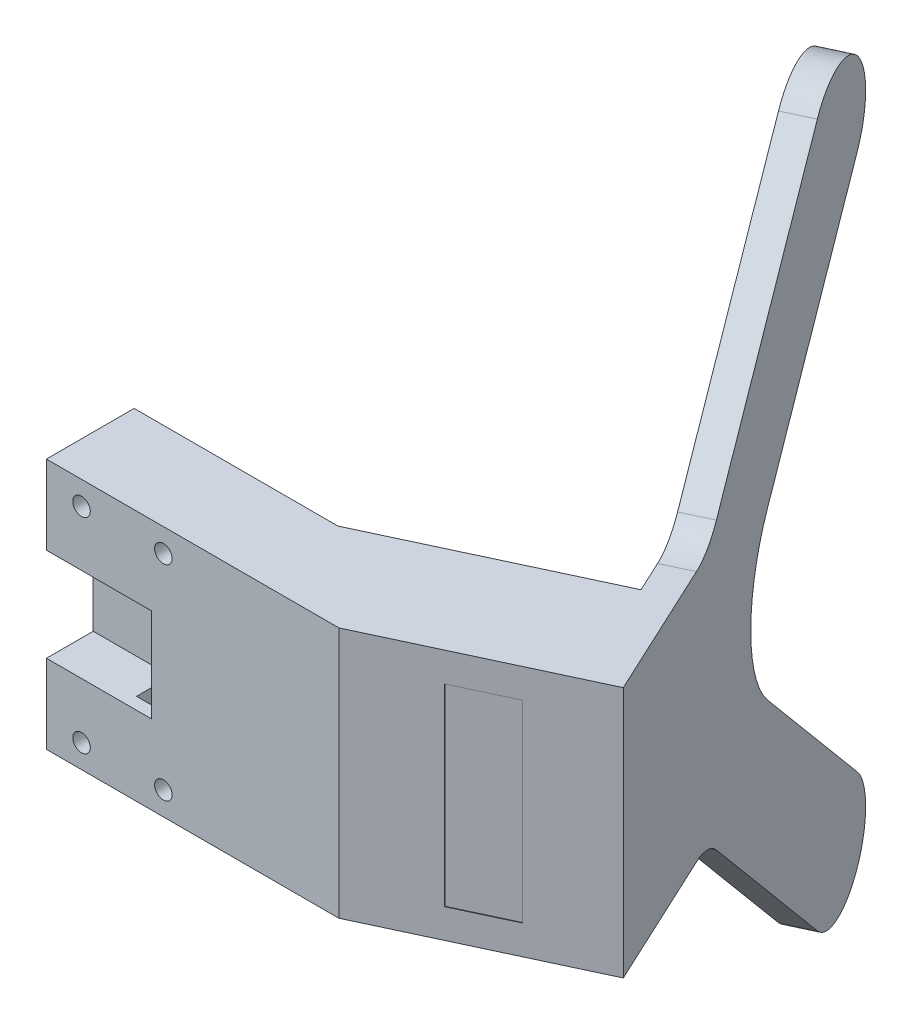
SolidWorks part; units mm, degrees
ref_plane "Ebene vorne" through (0, 0, 0) normal (0, 0, 1) x (1, 0, 0)
ref_plane "Ebene oben" through (0, 0, 0) normal (0, 1, 0) x (1, 0, 0)
ref_plane "Ebene rechts" through (0, 0, 0) normal (1, 0, 0) x (0, 0, -1)
sketch "Skizze1" plane through (0, 0, 0) normal (0, 1, 0) x (1, 0, 0)
  line L0 (0, 0) -> (50, 0)
  line L1 (50, 0) -> (78.6419, 13.356)
  line L2 (78.6419, 13.356) -> (70.1896, 31.4821)
  line L3 (70.1896, 31.4821) -> (34.8436, 15)
  line L4 (34.8436, 15) -> (0, 15)
  line L5 (0, 15) -> (0, 0)
  dimension "D1" = 50
  dimension "D2" = 20
  dimension "D3" = 15
  dimension "D4" = 155
  dimension "D5" = 39
extrude "Aufsatz-Linear austragen1" add sketch "Skizze1" along normal blind 43
sketch "Skizze2" plane through (69.7116, 0, -32.5071) normal (0.9063, 0, -0.4226) x (-0.4226, 0, -0.9063)
  line L0 (-21.1309, 43) -> (8.8691, 43)
  line L1 (-21.1309, 43) -> (-21.1309, 0) construction
  line L2 (-21.1309, 43) -> (-1.1309, 43) construction
  line L3 (8.8691, 43) -> (54.5442, 88.6751)
  line L4 (54.5442, 88.6751) -> (68.6864, 74.533)
  line L5 (68.6864, 74.533) -> (15.6534, 21.5)
  line L6 (15.6534, 21.5) -> (68.6864, -31.533)
  line L7 (68.6864, -31.533) -> (54.5442, -45.6751)
  line L8 (54.5442, -45.6751) -> (8.8691, 0)
  line L9 (8.8691, 0) -> (-21.1309, 0)
  line L10 (-21.1309, 0) -> (-21.1309, 43)
  dimension "D1" = 30
  dimension "D2" = 20
  dimension "D3" = 135
  dimension "D4" = 135
  dimension "D5" = 20
  dimension "D6" = 75
  dimension "D7" = 75
extrude "Aufsatz-Linear austragen2" add sketch "Skizze2" along normal blind 5
sketch "Skizze3" plane through (0, 0, 0) normal (0, 0, 1) x (1, 0, 0)
  line L0 (0, 43) -> (0, 0) construction
  line L1 (0, 43) -> (50, 43) construction
  line L2 (0, 0) -> (50, 0) construction
  circle A0 centre (6, 39) radius 1.5
  circle A1 centre (20, 39) radius 1.5
  circle A2 centre (6, 4) radius 1.5
  circle A3 centre (20, 4) radius 1.5
  dimension "D1" = 3
  dimension "D2" = 6
  dimension "D3" = 4
  dimension "D4" = 14
  dimension "D5" = 4
extrude "Schnitt-Linear austragen1" cut sketch "Skizze3" against normal up to next
sketch "Skizze4" plane through (0, 0, 0) normal (-1, 0, 0) x (0, 0, 1)
  line L0 (0, 43) -> (0, 0) construction
  line L1 (0, 29.5) -> (-8, 29.5)
  line L2 (0, 29.5) -> (0, 13.5)
  line L3 (0, 13.5) -> (-8, 13.5)
  line L4 (-8, 29.5) -> (-8, 13.5)
  line L5 (-15, 43) -> (0, 43) construction
  dimension "D1" = 16
  dimension "D2" = 8
  dimension "D3" = 13.5
extrude "Schnitt-Linear austragen2" cut sketch "Skizze4" against normal blind 18
sketch "Skizze5" plane through (0.4779, 0, 1.025) normal (-0.4226, 0, -0.9063) x (-0.9063, 0, 0.4226)
  line L0 (-76.9183, 43) -> (-76.9183, 0) construction
  line L1 (-75.9183, 41) -> (-45.9183, 41)
  line L2 (-75.9183, 41) -> (-75.9183, 2)
  line L3 (-75.9183, 2) -> (-45.9183, 2)
  line L4 (-45.9183, 41) -> (-45.9183, 2)
  line L5 (-76.9183, 0) -> (-37.9183, 0) construction
  line L6 (-76.9183, 43) -> (-37.9183, 43) construction
  dimension "D1" = 1
  dimension "D2" = 2
  dimension "D3" = 2
  dimension "D4" = 30
extrude "Schnitt-Linear austragen3" cut sketch "Skizze5" against normal blind 18
sketch "Skizze6" plane through (8.0851, 0, 17.3385) normal (-0.4226, 0, -0.9063) x (-0.9063, 0, 0.4226)
  line L0 (-45.9183, 41) -> (-75.9183, 41) construction
  line L1 (-75.9183, 41) -> (-68.9183, 41)
  line L2 (-75.9183, 41) -> (-75.9183, 33.5)
  line L3 (-75.9183, 33.5) -> (-68.9183, 33.5)
  line L4 (-68.9183, 41) -> (-68.9183, 33.5)
  line L5 (-75.9183, 41) -> (-75.9183, 2) construction
  line L7 (-75.9183, 25.5) -> (-68.9183, 25.5)
  line L8 (-75.9183, 25.5) -> (-75.9183, 11.5)
  line L9 (-75.9183, 11.5) -> (-68.9183, 11.5)
  line L10 (-68.9183, 25.5) -> (-68.9183, 11.5)
  line L11 (-75.9183, 2) -> (-68.9183, 2)
  line L12 (-75.9183, 2) -> (-75.9183, 7.5)
  line L13 (-75.9183, 7.5) -> (-68.9183, 7.5)
  line L14 (-68.9183, 2) -> (-68.9183, 7.5)
  dimension "D1" = 7
  dimension "D2" = 7.5
  dimension "D3" = 14
  dimension "D4" = 5.5
  dimension "D5" = 4
extrude "Aufsatz-Linear austragen3" add sketch "Skizze6" along normal blind 4
fillet "Verrundung1" radius 2 4 edges at (69.701, 7.5, -13.6002) (69.701, 11.5, -13.6002) (69.701, 25.5, -13.6002) (69.701, 33.5, -13.6002)
hole_wizard "Ø3.4 (3.4) Durchmesser Bohrung1" positions "Skizze7" profile "Skizze9" hole size "Ø3.4" standard "ANSI Metric"
sketch "Skizze7" plane through (6.3946, 0, 13.7133) normal (-0.4226, 0, -0.9063) x (-0.9063, 0, 0.4226)
  line L0 (-68.9183, 41) -> (-75.9183, 41) construction
  line L1 (-68.9183, 35.5) -> (-68.9183, 41) construction
  line L2 (-75.9183, 2) -> (-68.9183, 2) construction
  line L3 (-68.9183, 2) -> (-68.9183, 5.5) construction
  point P0 (-72.4183, 37)
  point P2 (-72.4183, 22)
  point P4 (-71.4183, 14.1)
  point P6 (-71.4183, 5)
  dimension "D1" = 4
  dimension "D2" = 3.5
  dimension "D3" = 15
  dimension "D4" = 9.1
  dimension "D5" = 3
  dimension "D6" = 2.5
sketch "Skizze9" plane through (72.0278, 37, -16.892) normal (0, 1, 0) x (-0.9063, 0, 0.4226)
  line L0 (0, 0) -> (0, 4)
  line L1 (0, 4) -> (1.7, 4)
  line L2 (1.7, 4) -> (1.7, 0)
  line L5 (1.7, 0) -> (0, 0)
  line L10 (0, 4) -> (-1.7, 4) construction
  line L11 (0, -6.35) -> (0, 107.95) construction
  dimension "Bohrerdurchmesser" = 3.4
  dimension "Bohrungstiefe" = 4
  dimension "Spitzenwinkel" = 180
sketch "Skizze10" plane through (8.0851, 0, 17.3385) normal (-0.4226, 0, -0.9063) x (-0.9063, 0, 0.4226)
  line L0 (-68.9183, 35.5) -> (-68.9183, 41) construction
  line L1 (-68.9183, 38) -> (-58.9183, 38)
  line L2 (-68.9183, 38) -> (-68.9183, 5)
  line L3 (-68.9183, 5) -> (-58.9183, 5)
  line L4 (-58.9183, 38) -> (-58.9183, 5)
  line L5 (-45.9183, 41) -> (-68.9183, 41) construction
  line L6 (-68.9183, 2) -> (-45.9183, 2) construction
  dimension "D1" = 3
  dimension "D2" = 3
  dimension "D3" = 10
extrude "Schnitt-Linear austragen4" cut sketch "Skizze10" against normal blind 1
sketch "Skizze11" plane through (8.9303, 0, 19.1511) normal (0.4226, 0, 0.9063) x (0.9063, 0, -0.4226)
  line L1 (58.9183, 38) -> (68.9183, 38)
  line L2 (58.9183, 38) -> (58.9183, 5)
  line L3 (58.9183, 5) -> (68.9183, 5)
  line L4 (68.9183, 38) -> (68.9183, 5)
extrude "Schnitt-Linear austragen5" cut sketch "Skizze11" against normal blind 0.1
sketch "Skizze12" plane through (0, 2, 0) normal (0, 1, 0) x (1, 0, 0)
  line L0 (49.7012, 2.0674) -> (42.094, 18.3809)
  line L1 (49.7012, 2.0674) -> (42.094, 18.3809) construction
  line L2 (42.094, 18.3809) -> (34.8436, 15)
  line L3 (34.8436, 15) -> (34.8436, 12.5)
  line L5 (29.3436, 2.0674) -> (49.7012, 2.0674)
  line L6 (70.1896, 31.4821) -> (34.8436, 15) construction
  line L7 (34.8436, 12.5) -> (29.3436, 12.5)
  line L8 (29.3436, 12.5) -> (29.3436, 2.0674)
  dimension "D1" = 2.5
  dimension "D2" = 5.5
  dimension "D3" = 65
extrude "Schnitt-Linear austragen7" cut sketch "Skizze12" along normal blind 39
sketch "Skizze15" plane through (29.3436, 0, 0) normal (1, 0, 0) x (0, 0, -1)
  line L0 (2.0674, 41) -> (2.0674, 2) construction
  line L1 (2.0674, 33.5) -> (12.5, 33.5)
  line L2 (2.0674, 33.5) -> (2.0674, 9.5)
  line L3 (2.0674, 9.5) -> (12.5, 9.5)
  line L4 (12.5, 33.5) -> (12.5, 9.5)
  line L5 (12.5, 41) -> (12.5, 2) construction
  line L6 (12.5, 41) -> (2.0674, 41) construction
  dimension "D1" = 24
  dimension "D2" = 7.5
extrude "Schnitt-Linear austragen10" cut sketch "Skizze15" against normal blind 16
sketch "Skizze16" plane through (68.8053, 0, -32.0844) normal (-0.9063, 0, 0.4226) x (0.4226, 0, 0.9063)
  line L0 (15.1309, 41) -> (1.1309, 41) construction
  line L1 (1.1309, 41) -> (3.2309, 41)
  line L2 (1.1309, 41) -> (1.1309, 2)
  line L3 (1.1309, 2) -> (3.2309, 2)
  line L4 (3.2309, 41) -> (3.2309, 2)
  line L5 (1.1309, 41) -> (1.1309, 2) construction
  line L6 (15.1309, 2) -> (1.1309, 2) construction
  dimension "D1" = 2.1
extrude "Schnitt-Linear austragen11" cut sketch "Skizze16" against normal blind 2
fillet "Verrundung2" radius 20 1 edges at (65.362, 21.5, -47.7504)
fillet "Verrundung3" radius 10 6 edges at (68.2292, 43, -41.6017) (68.2292, 0, -41.6017) (42.9493, 74.533, -95.8146) (48.926, 88.6751, -82.9975) (48.926, -45.6751, -82.9975) (42.9493, -31.533, -95.8146)
ref_plane "Ebene2" through (1.3232, 0, 2.8376) normal (-0.4226, 0, -0.9063) x (-0.9063, 0, 0.4226)
sketch "Skizze17" plane through (1.3232, 0, 2.8376) normal (-0.4226, 0, -0.9063) x (-0.9063, 0, 0.4226)
  line L0 (-37.9183, 41) -> (-37.9183, 2) construction
  line L1 (-37.9183, 41) -> (-43.9183, 41)
  line L2 (-37.9183, 41) -> (-37.9183, 35)
  line L3 (-37.9183, 35) -> (-43.9183, 35)
  line L4 (-43.9183, 41) -> (-43.9183, 35)
  line L5 (-68.9183, 41) -> (-75.9183, 41) construction
  line L6 (-75.9183, 2) -> (-68.9183, 2) construction
  line L7 (-43.9183, 8) -> (-37.9183, 8)
  line L8 (-43.9183, 8) -> (-43.9183, 2)
  line L9 (-43.9183, 2) -> (-37.9183, 2)
  line L10 (-37.9183, 8) -> (-37.9183, 2)
  dimension "D1" = 6
  dimension "D2" = 6
  dimension "D3" = 6
  dimension "D4" = 6
extrude "Aufsatz-Linear austragen4" add sketch "Skizze17" against normal blind 5
chamfer "Fase1" distance 6 angle 45 2 edges at (40.5208, 2, -9.9237) (40.5208, 41, -9.9237)
hole_wizard "Ø3.4 (3.4) Durchmesser Bohrung2" positions "Skizze18" profile "Skizze19" hole size "Ø3.4" standard "ANSI Metric"
sketch "Skizze18" plane through (1.3232, 0, 2.8376) normal (-0.4226, 0, -0.9063) x (-0.9063, 0, 0.4226)
  line L0 (-43.9183, 8) -> (-43.9183, 2) construction
  line L1 (-37.9183, 8) -> (-43.9183, 8) construction
  line L2 (-43.9183, 35) -> (-37.9183, 35) construction
  line L3 (-43.9183, 41) -> (-43.9183, 35) construction
  point P0 (-40.9183, 38)
  point P2 (-40.9183, 5)
  dimension "D1" = 3
  dimension "D2" = 3
  dimension "D3" = 3
  dimension "D4" = 3
sketch "Skizze19" plane through (38.4077, 38, -14.4552) normal (0, 1, 0) x (-0.9063, 0, 0.4226)
  line L0 (0, 0) -> (0, 6.0215)
  line L1 (0, 6.0215) -> (1.7, 5)
  line L2 (1.7, 5) -> (1.7, 0)
  line L5 (1.7, 0) -> (0, 0)
  line L10 (0, 6.0215) -> (-1.7, 5) construction
  line L11 (0, -6.35) -> (0, 107.95) construction
  dimension "Bohrerdurchmesser" = 3.4
  dimension "Bohrungstiefe" = 5
  dimension "Spitzenwinkel" = 118
